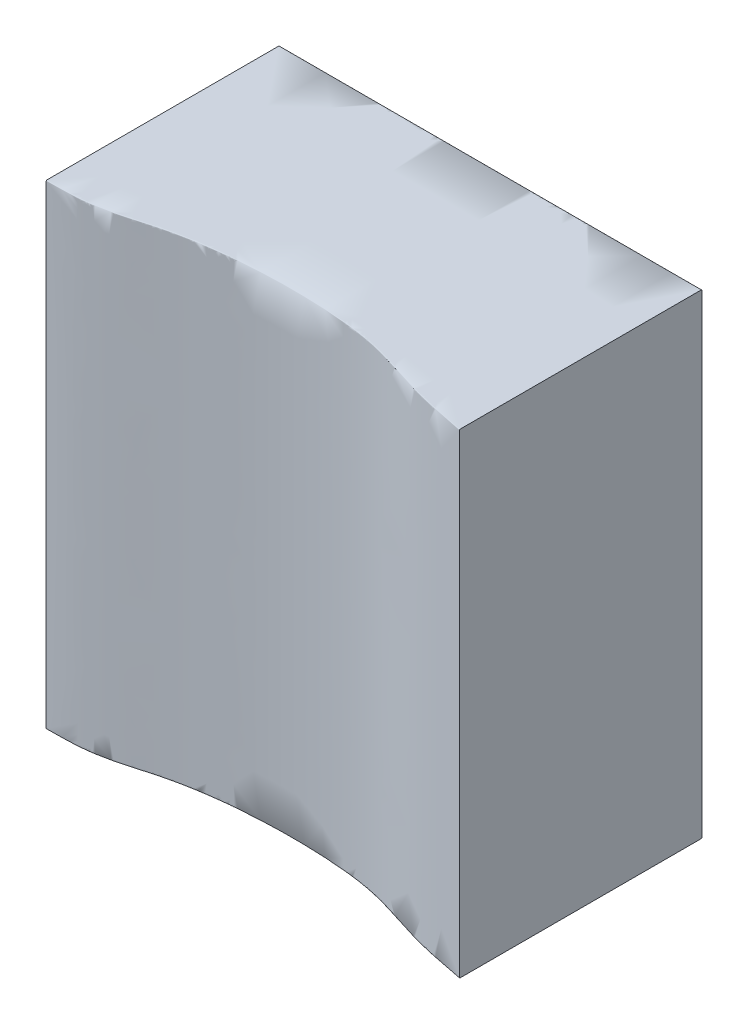
SolidWorks part; units mm, degrees
ref_plane "前视基准面" through (0, 0, 0) normal (0, 0, 1) x (1, 0, 0)
ref_plane "上视基准面" through (0, 0, 0) normal (0, 1, 0) x (1, 0, 0)
ref_plane "右视基准面" through (0, 0, 0) normal (1, 0, 0) x (0, 0, -1)
other "Configuration Table"
sketch3d "V67_split_0"
  line L0 (-160, -179.5, -50) -> (-160, 179.5, -50)
  line L1 (-160, 180, -49.5) -> (-160, 180, 126.1)
  line L2 (-160, 179.5, 126.6) -> (-160, -179.5, 126.6)
  line L3 (-160, -180, 126.1) -> (-160, -180, -49.5)
  arc A0 (-160, -180, -49.5) -> (-160, -179.5, -50) centre (-160, -179.5, -49.5) cw
  arc A1 (-160, 179.5, -50) -> (-160, 180, -49.5) centre (-160, 179.5, -49.5) cw
  arc A2 (-160, 180, 126.1) -> (-160, 179.5, 126.6) centre (-160, 179.5, 126.1) cw
  arc A3 (-160, -179.5, 126.6) -> (-160, -180, 126.1) centre (-160, -179.5, 126.1) cw
  point P2 (-159.5, -179.5, -49.5)
  point P9 (-159.5, 179.5, -49.5)
  point P16 (-159.5, 179.5, 126.1)
  point P23 (-159.5, -179.5, 126.1)
sketch3d "V67_split_1"
  line L0 (-125, -179.5, -50) -> (-125, 179.5, -50)
  line L1 (-125, 180, -49.5) -> (-125, 180, 124.1)
  line L2 (-125, 179.5, 124.6) -> (-125, -179.5, 124.6)
  line L3 (-125, -180, 124.1) -> (-125, -180, -49.5)
  arc A0 (-125, -180, -49.5) -> (-125, -179.5, -50) centre (-125, -179.5, -49.5) cw
  arc A1 (-125, 179.5, -50) -> (-125, 180, -49.5) centre (-125, 179.5, -49.5) cw
  arc A2 (-125, 180, 124.1) -> (-125, 179.5, 124.6) centre (-125, 179.5, 124.1) cw
  arc A3 (-125, -179.5, 124.6) -> (-125, -180, 124.1) centre (-125, -179.5, 124.1) cw
  point P2 (-124.5, -179.5, -49.5)
  point P9 (-124.5, 179.5, -49.5)
  point P16 (-124.5, 179.5, 124.1)
  point P23 (-124.5, -179.5, 124.1)
sketch3d "V67_split_2"
  line L0 (-85, -179.5, -50) -> (-85, 179.5, -50)
  line L1 (-85, 180, -49.5) -> (-85, 180, 114.1)
  line L2 (-85, 179.5, 114.6) -> (-85, -179.5, 114.6)
  line L3 (-85, -180, 114.1) -> (-85, -180, -49.5)
  arc A0 (-85, -180, -49.5) -> (-85, -179.5, -50) centre (-85, -179.5, -49.5) cw
  arc A1 (-85, 179.5, -50) -> (-85, 180, -49.5) centre (-85, 179.5, -49.5) cw
  arc A2 (-85, 180, 114.1) -> (-85, 179.5, 114.6) centre (-85, 179.5, 114.1) cw
  arc A3 (-85, -179.5, 114.6) -> (-85, -180, 114.1) centre (-85, -179.5, 114.1) cw
  point P2 (-84.5, -179.5, -49.5)
  point P9 (-84.5, 179.5, -49.5)
  point P16 (-84.5, 179.5, 114.1)
  point P23 (-84.5, -179.5, 114.1)
sketch3d "V67_split_3"
  line L0 (-35, -179.5, -50) -> (-35, 179.5, -50)
  line L1 (-35, 180, -49.5) -> (-35, 180, 106.1)
  line L2 (-35, 179.5, 106.6) -> (-35, -179.5, 106.6)
  line L3 (-35, -180, 106.1) -> (-35, -180, -49.5)
  arc A0 (-35, -180, -49.5) -> (-35, -179.5, -50) centre (-35, -179.5, -49.5) cw
  arc A1 (-35, 179.5, -50) -> (-35, 180, -49.5) centre (-35, 179.5, -49.5) cw
  arc A2 (-35, 180, 106.1) -> (-35, 179.5, 106.6) centre (-35, 179.5, 106.1) cw
  arc A3 (-35, -179.5, 106.6) -> (-35, -180, 106.1) centre (-35, -179.5, 106.1) cw
  point P2 (-34.5, -179.5, -49.5)
  point P9 (-34.5, 179.5, -49.5)
  point P16 (-34.5, 179.5, 106.1)
  point P23 (-34.5, -179.5, 106.1)
sketch3d "V67_split_4"
  line L0 (30, -179.5, -50) -> (30, 179.5, -50)
  line L1 (30, 180, -49.5) -> (30, 180, 105.1)
  line L2 (30, 179.5, 105.6) -> (30, -179.5, 105.6)
  line L3 (30, -180, 105.1) -> (30, -180, -49.5)
  arc A0 (30, -180, -49.5) -> (30, -179.5, -50) centre (30, -179.5, -49.5) cw
  arc A1 (30, 179.5, -50) -> (30, 180, -49.5) centre (30, 179.5, -49.5) cw
  arc A2 (30, 180, 105.1) -> (30, 179.5, 105.6) centre (30, 179.5, 105.1) cw
  arc A3 (30, -179.5, 105.6) -> (30, -180, 105.1) centre (30, -179.5, 105.1) cw
  point P2 (30.5, -179.5, -49.5)
  point P9 (30.5, 179.5, -49.5)
  point P16 (30.5, 179.5, 105.1)
  point P23 (30.5, -179.5, 105.1)
sketch3d "V67_split_5"
  line L0 (75, -179.5, -50) -> (75, 179.5, -50)
  line L1 (75, 180, -49.5) -> (75, 180, 111.1)
  line L2 (75, 179.5, 111.6) -> (75, -179.5, 111.6)
  line L3 (75, -180, 111.1) -> (75, -180, -49.5)
  arc A0 (75, -180, -49.5) -> (75, -179.5, -50) centre (75, -179.5, -49.5) cw
  arc A1 (75, 179.5, -50) -> (75, 180, -49.5) centre (75, 179.5, -49.5) cw
  arc A2 (75, 180, 111.1) -> (75, 179.5, 111.6) centre (75, 179.5, 111.1) cw
  arc A3 (75, -179.5, 111.6) -> (75, -180, 111.1) centre (75, -179.5, 111.1) cw
  point P2 (75.5, -179.5, -49.5)
  point P9 (75.5, 179.5, -49.5)
  point P16 (75.5, 179.5, 111.1)
  point P23 (75.5, -179.5, 111.1)
sketch3d "V67_split_6"
  line L0 (115, -179.5, -50) -> (115, 179.5, -50)
  line L1 (115, 180, -49.5) -> (115, 180, 123.1)
  line L2 (115, 179.5, 123.6) -> (115, -179.5, 123.6)
  line L3 (115, -180, 123.1) -> (115, -180, -49.5)
  arc A0 (115, -180, -49.5) -> (115, -179.5, -50) centre (115, -179.5, -49.5) cw
  arc A1 (115, 179.5, -50) -> (115, 180, -49.5) centre (115, 179.5, -49.5) cw
  arc A2 (115, 180, 123.1) -> (115, 179.5, 123.6) centre (115, 179.5, 123.1) cw
  arc A3 (115, -179.5, 123.6) -> (115, -180, 123.1) centre (115, -179.5, 123.1) cw
  point P2 (115.5, -179.5, -49.5)
  point P9 (115.5, 179.5, -49.5)
  point P16 (115.5, 179.5, 123.1)
  point P23 (115.5, -179.5, 123.1)
sketch3d "V67_split_7"
  line L0 (160, -179.5, -50) -> (160, 179.5, -50)
  line L1 (160, 180, -49.5) -> (160, 180, 133.1)
  line L2 (160, 179.5, 133.6) -> (160, -179.5, 133.6)
  line L3 (160, -180, 133.1) -> (160, -180, -49.5)
  arc A0 (160, -180, -49.5) -> (160, -179.5, -50) centre (160, -179.5, -49.5) cw
  arc A1 (160, 179.5, -50) -> (160, 180, -49.5) centre (160, 179.5, -49.5) cw
  arc A2 (160, 180, 133.1) -> (160, 179.5, 133.6) centre (160, 179.5, 133.1) cw
  arc A3 (160, -179.5, 133.6) -> (160, -180, 133.1) centre (160, -179.5, 133.1) cw
  point P2 (160.5, -179.5, -49.5)
  point P9 (160.5, 179.5, -49.5)
  point P16 (160.5, 179.5, 133.1)
  point P23 (160.5, -179.5, 133.1)
loft "V67_side_seam" add profiles "V67_split_0", "V67_split_1", "V67_split_2", "V67_split_3", "V67_split_4", "V67_split_5", "V67_split_6", "V67_split_7" connector at (-160, 179.5, -50) connector at (-125, 179.5, -50) connector at (-85, 179.5, -50) connector at (-35, 179.5, -50) connector at (30, 179.5, -50) connector at (75, 179.5, -50) connector at (115, 179.5, -50) connector at (160, 179.5, -50)
